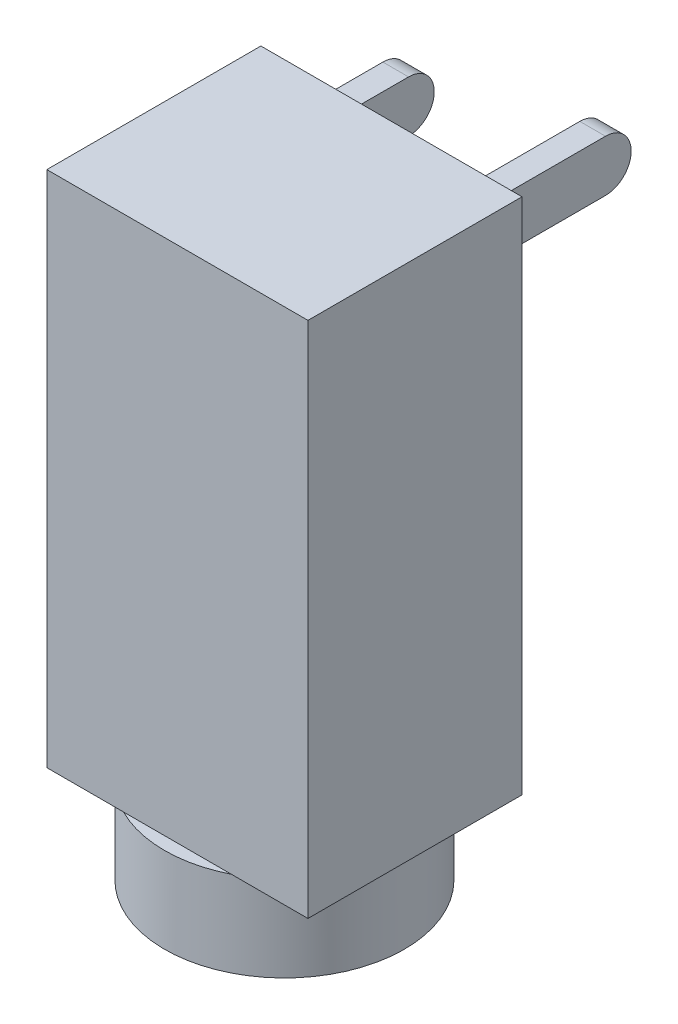
SolidWorks part; units mm, degrees
ref_plane "Front Plane" through (0, 0, 0) normal (0, 0, 1) x (1, 0, 0)
ref_plane "Top Plane" through (0, 0, 0) normal (0, 1, 0) x (1, 0, 0)
ref_plane "Right Plane" through (0, 0, 0) normal (1, 0, 0) x (0, 0, -1)
sketch "Sketch1" plane through (0, 0, 0) normal (0, 0, 1) x (1, 0, 0)
  line L1 (-3.05, 6.05) -> (3.05, 6.05)
  line L2 (-3.05, 6.05) -> (-3.05, -6.05)
  line L3 (-3.05, -6.05) -> (3.05, -6.05)
  line L4 (3.05, 6.05) -> (3.05, -6.05)
  line L5 (-3.05, 6.05) -> (3.05, -6.05) construction
  line L6 (-3.05, -6.05) -> (3.05, 6.05) construction
  point P0 (0, 0)
  dimension "D1" = 6.1
  dimension "D2" = 12.1
extrude "Boss-Extrude1" add sketch "Sketch1" along normal blind 5
sketch "Sketch2" plane through (0, -6.05, 0) normal (0, -1, 0) x (1, 0, 0)
  line L0 (0, 0) -> (0, 5) construction
  line L1 (-3.05, 5) -> (3.05, 5) construction
  circle A0 centre (0, 2.5) radius 2.8
  circle A1 centre (0, 2.5) radius 1.8
  dimension "D1" = 5.6
  dimension "D2" = 3.6
extrude "Boss-Extrude2" add sketch "Sketch2" along normal blind 2
sketch "Sketch3" plane through (0, 0, 0) normal (0, 0, -1) x (-1, 0, 0)
  line L0 (0, -6.05) -> (0, 6.05) construction
  line L1 (-3.05, 6.05) -> (3.05, 6.05) construction
  line L2 (-1.261, -6.05) -> (-3.05, -6.05) construction
  line L3 (1.261, -6.05) -> (-1.261, -6.05) construction
  circle A0 centre (0, -4.45) radius 0.75
  circle A1 centre (0, 2.55) radius 0.75
  point P11 (0, -6.05)
  dimension "D1" = 1.5
  dimension "D2" = 1.6
  dimension "D3" = 7
extrude "Boss-Extrude3" add sketch "Sketch3" along normal blind 1
ref_axis "Axis1" through (0, -8.05, 2.5) along (0, 1, 0)
sketch "Sketch4" plane through (0, 0, 0) normal (0, 0, -1) x (-1, 0, 0)
  line L0 (2.3, -2.85) -> (2.3, 0.15) construction
  line L1 (2, -2.25) -> (2.6, -2.25)
  line L2 (2, -2.25) -> (2, -3.45)
  line L3 (2, -3.45) -> (2.6, -3.45)
  line L4 (2.6, -2.25) -> (2.6, -3.45)
  line L5 (2, -2.25) -> (2.6, -3.45) construction
  line L6 (2, -3.45) -> (2.6, -2.25) construction
  line L7 (2, 0.75) -> (2.6, 0.75)
  line L8 (2, 0.75) -> (2, -0.45)
  line L9 (2, -0.45) -> (2.6, -0.45)
  line L10 (2.6, 0.75) -> (2.6, -0.45)
  line L11 (2, 0.75) -> (2.6, -0.45) construction
  line L12 (2, -0.45) -> (2.6, 0.75) construction
  line L13 (2, 4.75) -> (2.6, 4.75)
  line L14 (2, 4.75) -> (2, 3.55)
  line L15 (2, 3.55) -> (2.6, 3.55)
  line L16 (2.6, 4.75) -> (2.6, 3.55)
  line L17 (2, 4.75) -> (2.6, 3.55) construction
  line L18 (2, 3.55) -> (2.6, 4.75) construction
  line L19 (-2.6, 5.85) -> (-2, 5.85)
  line L20 (-2.6, 5.85) -> (-2.6, 4.65)
  line L21 (-2.6, 4.65) -> (-2, 4.65)
  line L22 (-2, 5.85) -> (-2, 4.65)
  line L23 (-2.6, 5.85) -> (-2, 4.65) construction
  line L24 (-2.6, 4.65) -> (-2, 5.85) construction
  line L25 (2.3, 0.15) -> (2.3, 4.15) construction
  line L26 (0, 0) -> (0, 5.3758) construction
  line L27 (-1.261, -6.05) -> (-3.05, -6.05) construction
  line L28 (1.261, -6.05) -> (2.8, -6.05) construction
  point P0 (2.3, -2.85)
  point P5 (2.3, 0.15)
  point P10 (2.3, 4.15)
  point P15 (-2.3, 5.25)
  point P30 (-2.006, 5.25)
  dimension "D1" = 1.2
  dimension "D2" = 0.6
  dimension "D3" = 2.3
  dimension "D4" = 2.3
  dimension "D5" = 3.2
  dimension "D6" = 3
  dimension "D7" = 4
  dimension "D8" = 11.3
extrude "Boss-Extrude4" add sketch "Sketch4" along normal blind 3
fillet "Fillet1" radius 0.6 8 edges at (-2.3, 4.75, -3) (2.3, 5.85, -3) (2.3, 4.65, -3) (-2.3, 3.55, -3) (-2.3, 0.75, -3) (-2.3, -0.45, -3) (-2.3, -2.25, -3) (-2.3, -3.45, -3)
